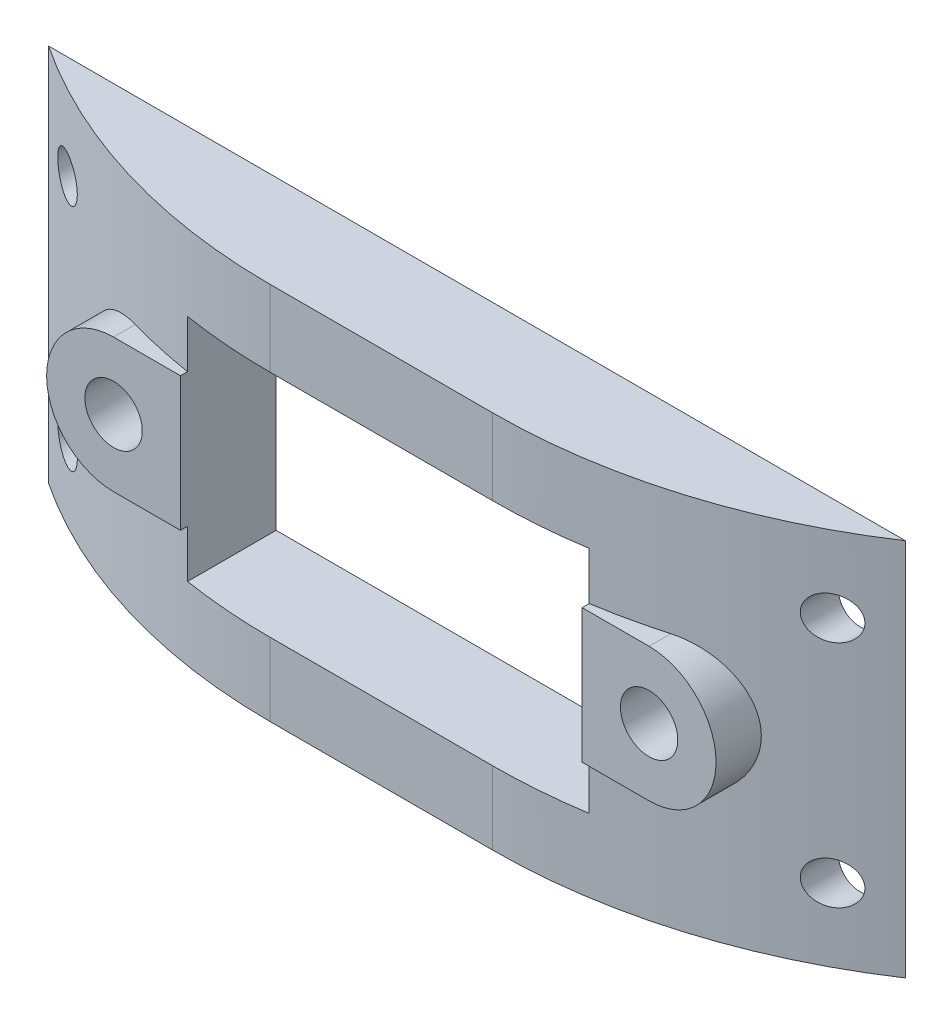
SolidWorks part; units mm, degrees
ref_plane "Front Plane" through (0, 0, 0) normal (0, 0, 1) x (1, 0, 0)
ref_plane "Top Plane" through (0, 0, 0) normal (0, 1, 0) x (1, 0, 0)
ref_plane "Right Plane" through (0, 0, 0) normal (1, 0, 0) x (0, 0, -1)
sketch "Sketch1" plane through (0, 0, 0) normal (0, 0, 1) x (1, 0, 0)
  line L1 (-22.4, 9.18) -> (22.4, 9.18)
  line L2 (-22.4, 9.18) -> (-22.4, 28.98)
  line L3 (-22.4, 28.98) -> (22.4, 28.98)
  line L4 (22.4, 9.18) -> (22.4, 28.98)
  dimension "D1" = 44.8
  dimension "D2" = 19.8
  dimension "D3" = 22.4
extrude "Boss-Extrude1" add sketch "Sketch1" along normal blind 5
sketch "Sketch2" plane through (0, 0, 5) normal (0, 0, 1) x (1, 0, 0)
  circle A0 centre (-20, 25) radius 1.1
  circle A1 centre (-20, 13) radius 1.1
  circle A2 centre (20, 25) radius 1.1
  circle A3 centre (20, 13) radius 1.1
  dimension "D6" = 2.2
  dimension "D7" = 2.2
  dimension "D8" = 2.2
  dimension "D9" = 2.2
  dimension "D1" = 13
  dimension "D2" = 12
  dimension "D3" = 12
  dimension "D4" = 40
  dimension "D5" = 13
  dimension "D10" = 20
  dimension "D11" = 40
  dimension "D12" = 20
extrude "Cut-Extrude1" cut sketch "Sketch2" against normal blind 13
sketch "Sketch3" plane through (0, 0, 5) normal (0, 0, 1) x (1, 0, 0)
  circle A0 centre (-14, 19) radius 1.5
  circle A1 centre (14, 19) radius 1.5
  dimension "D4" = 3
  dimension "D5" = 3
  dimension "D1" = 28
  dimension "D2" = 14
  dimension "D3" = 19
extrude "Cut-Extrude2" cut sketch "Sketch3" against normal blind 10
sketch "Sketch4" plane through (0, 0, 5) normal (0, 0, 1) x (1, 0, 0)
  line L1 (-10.5, 25) -> (10.5, 25)
  line L2 (-10.5, 25) -> (-10.5, 13)
  line L3 (-10.5, 13) -> (10.5, 13)
  line L4 (10.5, 25) -> (10.5, 13)
  dimension "D1" = 21
  dimension "D2" = 12
  dimension "D3" = 10.5
  dimension "D4" = 13
extrude "Cut-Extrude3" cut sketch "Sketch4" against normal blind 10
fillet "Fillet1" radius 30 2 edges at (22.4, 19.08, 5) (-22.4, 19.08, 5)
sketch "Sketch5" plane through (0, 0, 0) normal (0, 0, -1) x (-1, 0, 0)
  line L0 (-14, 22.5) -> (-10.5, 22.5)
  line L1 (-10.5, 25) -> (-10.5, 13) construction
  line L2 (-10.5, 22.5) -> (-10.5, 15.5)
  line L3 (-10.5, 15.5) -> (-14, 15.5)
  line L4 (14, 22.5) -> (10.5, 22.5)
  line L5 (10.5, 13) -> (10.5, 25) construction
  line L6 (10.5, 22.5) -> (10.5, 15.5)
  line L7 (10.5, 15.5) -> (14, 15.5)
  circle A0 centre (-14, 19) radius 3.5
  circle A1 centre (14, 19) radius 3.5
  line M1 (10.5, 25) -> (10.5, 13)
  line M3 (-10.5, 13) -> (-10.5, 25)
  circle M5 centre (14, 19) radius 1.5
  circle M6 centre (-14, 19) radius 1.5
extrude "Boss-Extrude2" add sketch "Sketch5" against normal blind 5 contours A0 M6 | A0 L2 L0 | A0 L3 M3 | A1 M5 | A1 L6 L7 | A1 L4 M1 region at (11.2818, 21.7182, 0) region at (11.5951, 21.4049, 0) region at (11.2818, 16.2818, 0) region at (-11.2818, 21.7182, 0) region at (-16.4049, 21.4049, 0) region at (-11.2818, 16.2818, 0)
